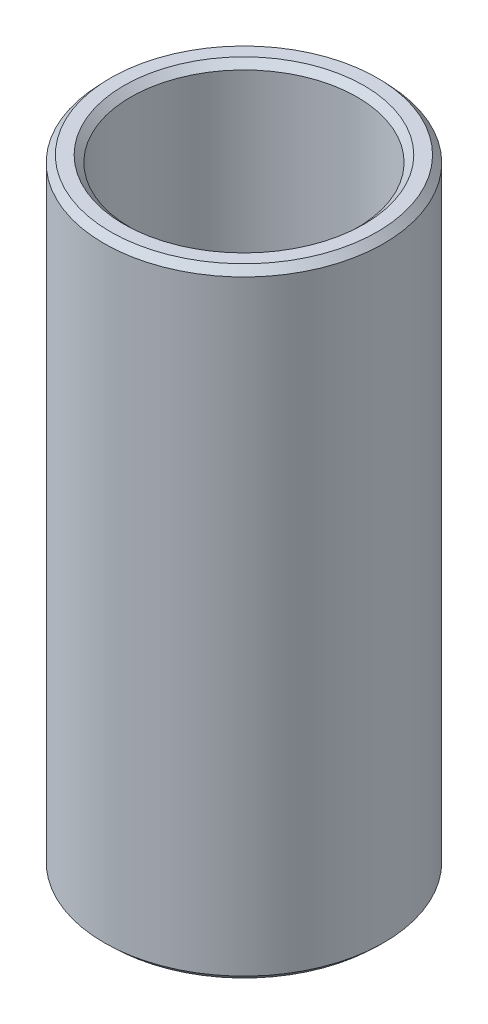
SolidWorks part; units mm, degrees
ref_plane "Front Plane" through (0, 0, 0) normal (0, 0, 1) x (1, 0, 0)
ref_plane "Top Plane" through (0, 0, 0) normal (0, 1, 0) x (1, 0, 0)
ref_plane "Right Plane" through (0, 0, 0) normal (1, 0, 0) x (0, 0, -1)
sketch "Sketch1" plane through (0, 0, 0) normal (0, 1, 0) x (1, 0, 0)
  circle A0 centre (0, 0) radius 42.5
  dimension "SLEEVE_OD" = 85
extrude "Boss-Extrude1" add sketch "Sketch1" along normal blind 188.0405
sketch "Sketch2" plane through (0, 0, 0) normal (0, 1, 0) x (1, 0, 0)
  circle A0 centre (0, 0) radius 34.4109
  dimension "BORE_D" = 68.8219
extrude "Cut-Extrude1" cut sketch "Sketch2" along normal through all
chamfer "Chamfer1" distance 2.0821 angle 43.461 4 edges at (0, 188.0405, 34.4109) (0, 0, 34.4109) (0, 0, 42.5) (0, 188.0405, 42.5) first distance on face at (0, 188.0405, 34.4109) first distance on face at (0, 0, 34.4109) first distance on face at (0, 188.0405, 42.5)
